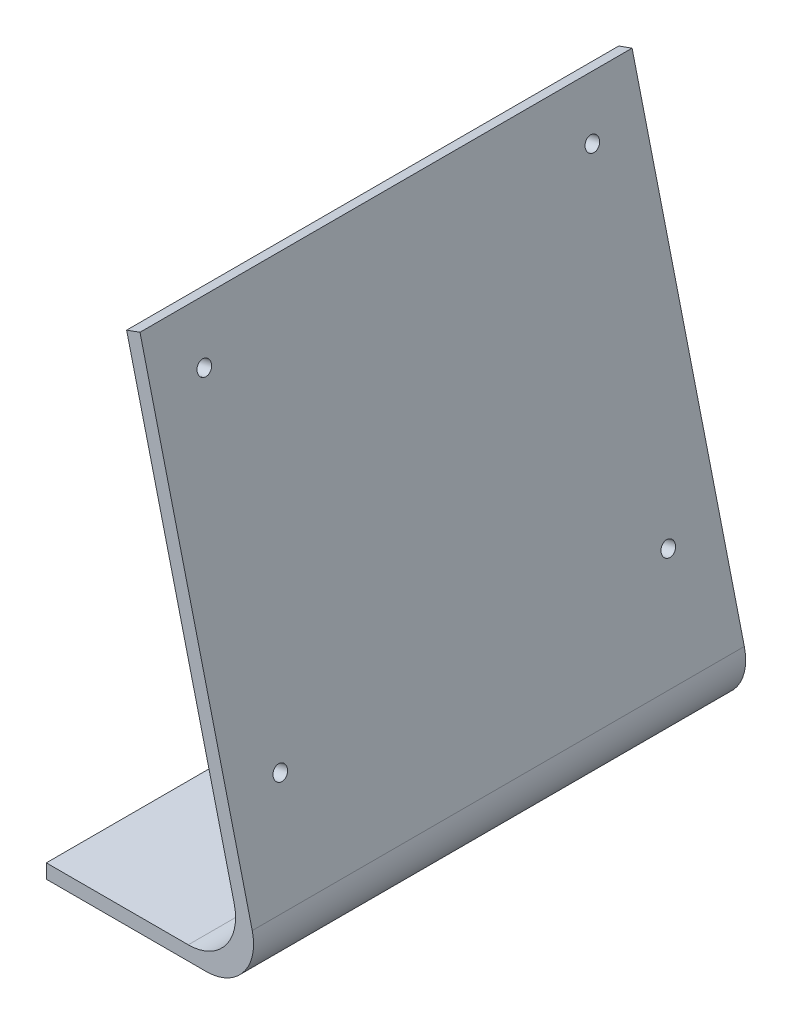
SolidWorks part; units mm, degrees
ref_plane "Front Plane" through (0, 0, 0) normal (0, 0, 1) x (1, 0, 0)
ref_plane "Top Plane" through (0, 0, 0) normal (0, 1, 0) x (1, 0, 0)
ref_plane "Right Plane" through (0, 0, 0) normal (1, 0, 0) x (0, 0, -1)
sketch "Sketch1" plane through (0, 0, 0) normal (0, 0, 1) x (1, 0, 0)
  line L0 (-50.53, 0) -> (-50.53, 3)
  line L1 (-50.53, 3) -> (-20.53, 3)
  line L2 (-50.53, 0) -> (-16.7319, 0)
  line L3 (-7.0146, 12.361) -> (-30.7379, 110)
  line L4 (-30.7379, 110) -> (-33.5595, 108.9811)
  line L5 (-33.5595, 108.9811) -> (-10.8127, 15.361)
  arc A0 (-10.8127, 15.361) -> (-20.53, 3) centre (-20.53, 13) cw
  arc A1 (-16.7319, 0) -> (-7.0146, 12.361) centre (-16.7319, 10) ccw
  dimension "D1" = 10
  dimension "D2" = 3
  dimension "D3" = 30
  dimension "D4" = 110
extrude "Boss-Extrude1" add sketch "Sketch1" along normal mid plane 104
sketch "Эскиз1" plane through (-3.7876, -0.9203, 0) normal (0.9717, 0.2361, 0) x (0, 0, -1)
  line L0 (-52, 114.1474) -> (52, 114.1474) construction
  line L1 (-47, 109.1474) -> (47, 109.1474) construction
  line L2 (-47, 109.1474) -> (-47, 29.1474) construction
  line L3 (-47, 29.1474) -> (47, 29.1474) construction
  line L4 (47, 109.1474) -> (47, 29.1474) construction
  line L5 (-47, 109.1474) -> (47, 29.1474) construction
  line L6 (-47, 29.1474) -> (47, 109.1474) construction
  line L7 (-52, 13.6677) -> (-52, 114.1474) construction
  point P0 (0, 69.1474)
  point P5 (0, 0)
  point P7 (0, 86.5644)
  dimension "D1" = 80
  dimension "D2" = 94
  dimension "D3" = 5
  dimension "D4" = 5
sketch "Эскиз2" plane through (-3.7876, -0.9203, 0) normal (0.9717, 0.2361, 0) x (0, 0, -1)
  line L0 (-47, 109.1474) -> (-47, 29.1474) construction
  line L1 (-47, 109.1474) -> (47, 109.1474) construction
  line L2 (0, 69.1474) -> (0, 79.7671) construction
  line L3 (-47, 109.1474) -> (47, 29.1474) construction
  line L4 (0, 69.1474) -> (-10.9608, 69.1474) construction
  circle A0 centre (-41, 103.1474) radius 1.5
  circle A1 centre (41, 103.1474) radius 1.5
  circle A2 centre (41, 35.1474) radius 1.5
  circle A3 centre (-41, 35.1474) radius 1.5
  dimension "D1" = 6
  dimension "D2" = 6
extrude "Вырез-Вытянуть1" cut sketch "Эскиз2" against normal up to next
